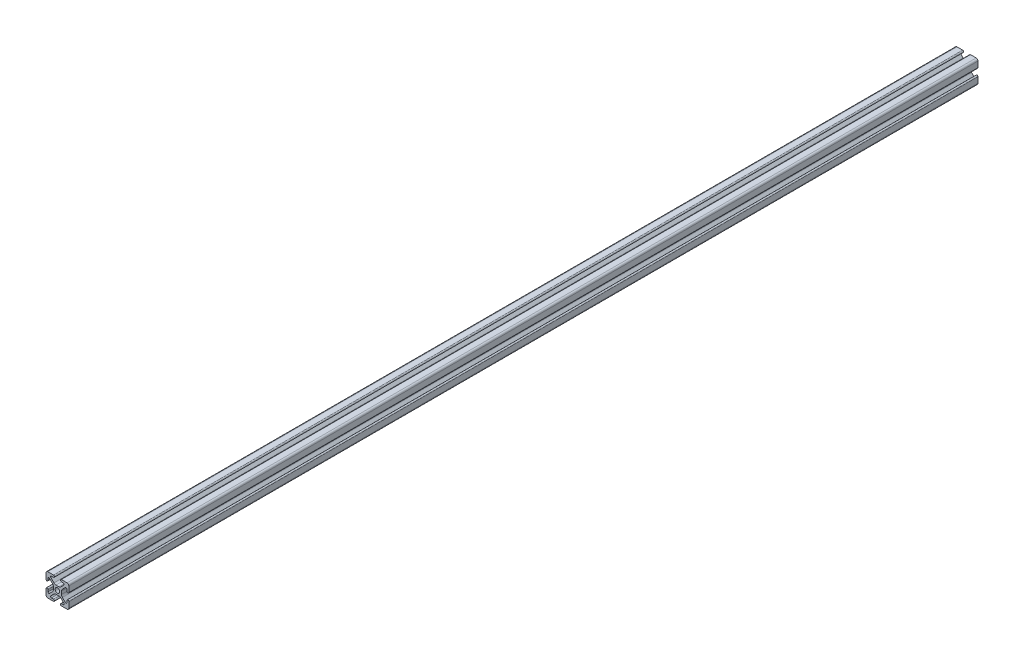
SolidWorks part; units mm, degrees
material "6061 Alloy"
ref_plane "Front Plane" through (0, 0, 0) normal (0, 0, 1) x (1, 0, 0)
ref_plane "Top Plane" through (0, 0, 0) normal (0, 1, 0) x (1, 0, 0)
ref_plane "Right Plane" through (0, 0, 0) normal (1, 0, 0) x (0, 0, -1)
sketch "Sketch1" plane through (0, 0, 0) normal (0, 0, 1) x (1, 0, 0)
  line L0 (-8.6363, 7.1116) -> (-5.4322, 3.9121)
  line L1 (-4.455, 1.5554) -> (-4.455, -1.5554)
  line L2 (-5.4322, -3.9121) -> (-8.6363, -7.1116)
  line L3 (-10.36, -6.3969) -> (-10.36, -4.32)
  line L4 (-12.5, -4.32) -> (-12.5, -8.6518)
  line L5 (-12.5, -8.6518) -> (-12.5, -10.5371)
  line L6 (-10.5371, -12.5) -> (-8.4416, -12.5)
  line L7 (-8.4416, -12.5) -> (-4.3879, -12.5)
  line L8 (-4.3879, -10.36) -> (-6.42, -10.36)
  line L9 (-7.1337, -8.6353) -> (-3.7953, -5.3018)
  line L10 (-1.5554, -4.375) -> (1.5554, -4.375)
  line L11 (10.36, 4.32) -> (10.36, 6.3969)
  line L12 (12.5, 7.9913) -> (12.5, 4.32)
  line L13 (12.5, 10.5371) -> (12.5, 7.9913)
  line L14 (4.32, 12.5) -> (10.5371, 12.5)
  line L16 (6.42, 10.36) -> (4.32, 10.36)
  line L17 (3.7953, 5.3018) -> (7.1337, 8.6353)
  line L18 (7.1337, -8.6353) -> (3.7953, -5.3018)
  line L19 (4.3879, -10.36) -> (6.42, -10.36)
  line L20 (8.4416, -12.5) -> (4.3879, -12.5)
  line L21 (10.5371, -12.5) -> (8.4416, -12.5)
  line L22 (12.5, -8.6518) -> (12.5, -10.5371)
  line L23 (12.5, -4.32) -> (12.5, -8.6518)
  line L24 (10.36, -6.3969) -> (10.36, -4.32)
  line L25 (5.4322, -3.9121) -> (8.6363, -7.1116)
  line L26 (4.455, 1.5554) -> (4.455, -1.5554)
  line L27 (8.6363, 7.1116) -> (5.4322, 3.9121)
  line L28 (1.5554, 4.375) -> (-1.5554, 4.375)
  line L29 (-3.7953, 5.3018) -> (-7.1337, 8.6353)
  line L30 (-6.42, 10.36) -> (-4.32, 10.36)
  line L32 (-4.32, 12.5) -> (-10.5371, 12.5)
  line L33 (-12.5, 10.5371) -> (-12.5, 7.9913)
  line L34 (-12.5, 7.9913) -> (-12.5, 4.32)
  line L35 (-10.36, 4.32) -> (-10.36, 6.3969)
  line L36 (-15.7693, 0) -> (12.5, 0) construction
  line L37 (0, 13.9334) -> (0, -12.3541) construction
  circle A0 centre (0, 0) radius 2.5
  arc A1 (-8.6363, 7.1116) -> (-10.36, 6.3969) centre (-9.35, 6.3969) ccw
  arc A2 (-4.455, 1.5554) -> (-5.4322, 3.9121) centre (-7.7855, 1.5554) ccw
  arc A3 (-5.4322, -3.9121) -> (-4.455, -1.5554) centre (-7.7855, -1.5554) ccw
  arc A4 (-10.36, -6.3969) -> (-8.6363, -7.1116) centre (-9.35, -6.3969) ccw
  arc A5 (-10.36, -4.32) -> (-12.5, -4.32) centre (-11.43, -4.32) ccw
  arc A6 (-12.5, -10.5371) -> (-10.5371, -12.5) centre (-10.5371, -10.5371) ccw
  arc A7 (-4.3879, -12.5) -> (-4.3879, -10.36) centre (-4.3879, -11.43) ccw
  arc A8 (-7.1337, -8.6353) -> (-6.42, -10.36) centre (-6.42, -9.35) ccw
  arc A9 (-1.5554, -4.375) -> (-3.7953, -5.3018) centre (-1.5554, -7.545) ccw
  arc A10 (12.5, 4.32) -> (10.36, 4.32) centre (11.43, 4.32) cw
  arc A11 (10.5371, 12.5) -> (12.5, 10.5371) centre (10.5371, 10.5371) cw
  arc A12 (4.32, 10.36) -> (4.32, 12.5) centre (4.32, 11.43) cw
  arc A13 (6.42, 10.36) -> (7.1337, 8.6353) centre (6.42, 9.35) cw
  arc A14 (3.7953, 5.3018) -> (1.5554, 4.375) centre (1.5554, 7.545) cw
  arc A15 (1.5554, -4.375) -> (3.7953, -5.3018) centre (1.5554, -7.545) cw
  arc A16 (7.1337, -8.6353) -> (6.42, -10.36) centre (6.42, -9.35) cw
  arc A17 (4.3879, -12.5) -> (4.3879, -10.36) centre (4.3879, -11.43) cw
  arc A18 (12.5, -10.5371) -> (10.5371, -12.5) centre (10.5371, -10.5371) cw
  arc A19 (10.36, -4.32) -> (12.5, -4.32) centre (11.43, -4.32) cw
  arc A20 (10.36, -6.3969) -> (8.6363, -7.1116) centre (9.35, -6.3969) cw
  arc A21 (5.4322, -3.9121) -> (4.455, -1.5554) centre (7.7855, -1.5554) cw
  arc A22 (4.455, 1.5554) -> (5.4322, 3.9121) centre (7.7855, 1.5554) cw
  arc A23 (8.6363, 7.1116) -> (10.36, 6.3969) centre (9.35, 6.3969) cw
  arc A24 (-3.7953, 5.3018) -> (-1.5554, 4.375) centre (-1.5554, 7.545) ccw
  arc A25 (-6.42, 10.36) -> (-7.1337, 8.6353) centre (-6.42, 9.35) ccw
  arc A26 (-4.32, 10.36) -> (-4.32, 12.5) centre (-4.32, 11.43) ccw
  arc A27 (-10.5371, 12.5) -> (-12.5, 10.5371) centre (-10.5371, 10.5371) ccw
  arc A28 (-12.5, 4.32) -> (-10.36, 4.32) centre (-11.43, 4.32) ccw
  dimension "D4" = 14.86
  dimension "D5" = 2.14
  dimension "D6" = 6.5
  dimension "D7" = 8.75
  dimension "D8" = 1.01
  dimension "D9" = 3.17
  dimension "D14" = 5
  dimension "D1" = 25
  dimension "D2" = 8.91
  dimension "D3" = 12.5
  dimension "D12" = 2.14
extrude "Extrude1" add sketch "Sketch1" against normal blind 996.064
